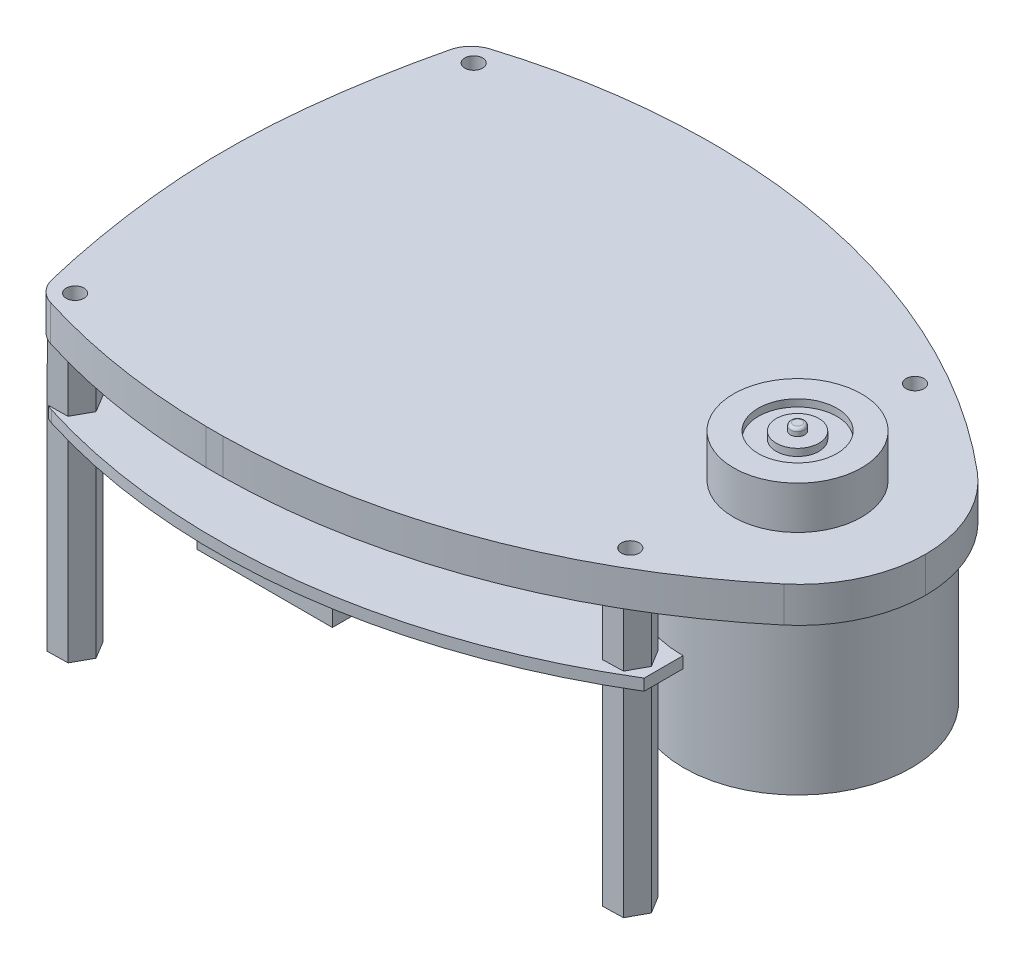
SolidWorks part; units mm, degrees
ref_plane "Спереди" through (0, 0, 0) normal (0, 0, 1) x (1, 0, 0)
ref_plane "Сверху" through (0, 0, 0) normal (0, 1, 0) x (1, 0, 0)
ref_plane "Справа" through (0, 0, 0) normal (1, 0, 0) x (0, 0, -1)
sketch "Эскиз1" plane through (0, 0, 0) normal (0, 1, 0) x (1, 0, 0)
  line L1 (-49.25, 35) -> (49.25, 35)
  line L2 (-49.25, 35) -> (-49.25, -35)
  line L3 (-49.25, -35) -> (49.25, -35)
  line L4 (49.25, 35) -> (49.25, -35)
  line L5 (-49.25, 35) -> (49.25, -35) construction
  line L6 (-49.25, -35) -> (49.25, 35) construction
  point P0 (0, 0)
  dimension "D1" = 98.5
  dimension "D2" = 70
extrude "Бобышка-Вытянуть1" add sketch "Эскиз1" along normal blind 5
sketch "Эскиз2" plane through (0, 5, 0) normal (0, 1, 0) x (1, 0, 0)
  line L0 (-49.25, 35) -> (-49.25, -35) construction
  circle A0 centre (-14.25, 0) radius 35
  point P2 (-49.25, 0)
  point P3 (-49.25, 0)
extrude "Бобышка-Вытянуть2" add sketch "Эскиз2" along normal blind 28.1
sketch "Эскиз3" plane through (0, 33.1, 0) normal (0, 1, 0) x (1, 0, 0)
  line L0 (-14.25, 0) -> (-14.25, 50000) construction
  line L1 (-14.25, -20) -> (-26.2883, -20) construction
  line L2 (-49.25, -35) -> (-14.25, -35) construction
  circle A0 centre (-14.25, 28.5) radius 2
  circle A1 centre (-34.5539, -20) radius 2
  circle A2 centre (6.0539, -20) radius 2
  arc A3 (-49.25, 0) -> (-14.25, -35) centre (-14.25, 0) ccw construction
  circle A4 centre (-14.25, 0) radius 35 construction
  dimension "D2" = 4
  dimension "D1" = 6.5
  dimension "D3" = 15
  dimension "D4" = 28.5
  dimension "D5" = 28.5
extrude "Вырез-Вытянуть1" cut sketch "Эскиз3" against normal blind 5
fillet "Скругление1" radius 2 1 edges at (-14.25, 33.1, 35)
fillet "Скругление2" radius 1 3 edges at (6.0539, 33.1, 22) (-34.5539, 33.1, 22) (-14.25, 33.1, -26.5)
sketch "Эскиз4" plane through (0, 33.1, 0) normal (0, 1, 0) x (1, 0, 0)
  line L0 (-22.1152, -6.9149) -> (-22.1152, -0.8316)
  line L1 (-22.1152, -0.8316) -> (-19.0735, -0.8316)
  line L2 (-19.0735, -0.8316) -> (-19.0735, -5.8538)
  line L3 (-19.0735, -5.8538) -> (-21.2663, -5.8538)
  line L4 (-21.2663, -5.8538) -> (-21.2663, -6.9149)
  line L5 (-21.2663, -6.9149) -> (-22.1152, -6.9149)
  line L6 (-22.1152, 0) -> (-22.1152, 5.1201)
  line L7 (-22.1152, 5.1201) -> (-19.0735, 5.1201)
  line L8 (-19.0735, 5.1201) -> (-19.0735, 4.2707)
  line L9 (-19.0735, 4.2707) -> (-21.2663, 4.2707)
  line L10 (-21.2663, 4.2707) -> (-21.2663, 0)
  line L11 (-21.2663, 0) -> (-22.1152, 0)
  line L12 (-21.2663, -1.9579) -> (-20.1699, -1.9579)
  line L13 (-20.1699, -1.9579) -> (-20.1699, -4.9509)
  line L14 (-20.1699, -4.9509) -> (-21.2663, -4.9509)
  line L15 (-21.2663, -4.9509) -> (-21.2663, -1.9579)
  line L16 (-13.8296, 0) -> (-13.8296, 6.293)
  line L17 (-18.1168, 0) -> (-14.8003, 0)
  line L18 (-18.1168, 0) -> (-18.1168, 5.1201)
  line L19 (-18.1168, 5.1201) -> (-14.8003, 5.1201)
  line L20 (-14.8003, 0) -> (-14.8003, 5.1201)
  line L21 (-9.8255, 5.1201) -> (-6.5494, 5.1201)
  line L22 (-9.8255, 5.1201) -> (-9.8255, 0)
  line L23 (-9.8255, 0) -> (-6.5494, 0)
  line L24 (-6.5494, 5.1201) -> (-6.5494, 0)
  line L25 (-8.9357, 4.2707) -> (-7.3988, 4.2707)
  line L26 (-8.9357, 4.2707) -> (-8.9357, 0.9137)
  line L27 (-8.9357, 0.9137) -> (-7.3988, 0.9137)
  line L28 (-7.3988, 4.2707) -> (-7.3988, 0.9137)
  line L29 (-17.3079, 4.2707) -> (-15.6497, 4.2707)
  line L30 (-17.3079, 4.2707) -> (-17.3079, 0.9137)
  line L31 (-17.3079, 0.9137) -> (-15.6497, 0.9137)
  line L32 (-15.6497, 4.2707) -> (-15.6497, 0.9137)
  line L33 (-12.9802, 4.2707) -> (-11.6455, 4.2707)
  line L34 (-12.9802, 4.2707) -> (-12.9802, 0.9137)
  line L35 (-12.9802, 0.9137) -> (-11.6455, 0.9137)
  line L36 (-11.6455, 4.2707) -> (-11.6455, 0.9137)
  line L37 (-12.9802, -4.142) -> (-11.6455, -4.142)
  line L38 (-12.9802, -4.142) -> (-12.9802, -5.1936)
  line L39 (-12.9802, -5.1936) -> (-11.6455, -5.1936)
  line L40 (-11.6455, -4.142) -> (-11.6455, -5.1936)
  line L41 (-16.9439, -1.9579) -> (-15.6497, -1.9579)
  line L42 (-16.9439, -1.9579) -> (-16.9439, -3.0499)
  line L43 (-16.9439, -3.0499) -> (-15.6497, -3.0499)
  line L44 (-15.6497, -1.9579) -> (-15.6497, -3.0499)
  line L46 (-7.5508, -0.7643) -> (-6.5494, -0.7643)
  line L47 (-7.5508, -0.7643) -> (-7.5508, -2.8858)
  line L48 (-7.5508, -2.8858) -> (-6.5494, -2.8858)
  line L49 (-6.5494, -0.7643) -> (-6.5494, -2.8858)
  line L50 (-6.5494, -6.9149) -> (-7.5508, -6.9149)
  line L51 (-6.5494, -6.9149) -> (-6.5494, -4.0216)
  line L52 (-6.5494, -4.0216) -> (-7.5508, -4.0216)
  line L53 (-13.8296, 6.293) -> (-12.9802, 6.293)
  line L54 (-12.9802, 6.293) -> (-12.9802, 5.1201)
  line L55 (-12.9802, 5.1201) -> (-10.7153, 5.1201)
  line L56 (-10.7153, 5.1201) -> (-10.7153, 0)
  line L57 (-10.7153, 0) -> (-13.8296, 0)
  line L58 (-9.8255, -0.8316) -> (-8.6437, -0.8316)
  line L59 (-8.6437, -0.8316) -> (-8.6437, -2.9608)
  line L60 (-8.6437, -2.9608) -> (-7.5508, -2.9608)
  line L61 (-9.8255, -0.8316) -> (-9.8255, -5.8538)
  line L62 (-9.8255, -5.8538) -> (-8.6437, -5.8538)
  line L63 (-8.6437, -5.8538) -> (-8.6437, -3.9573)
  line L64 (-8.6437, -3.9573) -> (-7.5508, -3.9573)
  line L65 (-7.5508, -2.9608) -> (-7.5508, -3.9573)
  line L66 (-13.8296, -0.8316) -> (-10.7153, -0.8316)
  line L67 (-10.7153, -0.8316) -> (-10.7153, -5.8538)
  line L68 (-10.7153, -5.8538) -> (-13.8296, -5.8538)
  line L69 (-13.8296, -5.8538) -> (-13.8296, -3.0499)
  line L70 (-13.8296, -3.0499) -> (-11.6455, -3.0499)
  line L71 (-11.6455, -3.0499) -> (-11.6455, -1.9408)
  line L72 (-11.6455, -1.9408) -> (-13.8296, -1.9408)
  line L73 (-13.8296, -1.9408) -> (-13.8296, -0.8316)
  line L74 (-18.1168, -0.8316) -> (-14.8003, -0.8316)
  line L75 (-14.8003, -0.8316) -> (-14.8003, -4.142)
  line L76 (-14.8003, -4.142) -> (-16.9439, -4.142)
  line L77 (-16.9439, -4.142) -> (-16.9439, -4.9509)
  line L78 (-16.9439, -4.9509) -> (-14.8003, -4.9509)
  line L79 (-14.8003, -4.9509) -> (-14.8003, -5.8538)
  line L80 (-14.8003, -5.8538) -> (-18.1168, -5.8538)
  line L81 (-18.1168, -5.8538) -> (-18.1168, -0.8316)
  line L82 (-7.5508, -6.9149) -> (-7.5508, -4.0216)
  circle A0 centre (-14.25, 0) radius 13
  dimension "D1" = 26
extrude "Вырез-Вытянуть3" cut sketch "Эскиз4" against normal blind 0.5 contours A0 L50 L82 L52 L51 L72 L73 L66 L67 L68 L69 L70 L71 L56 L57 L16 L53 L54 L55 L10 L11 L6 L7 L8 L9 L4 L5 L0 L1 L2 L3 L20 L17 L18 L19 L21 L24 L23 L22 L46 L49 L48 L47 | L32 L29 L30 L31 | L36 L33 L34 L35 | L28 L25 L26 L27 | L44 L41 L42 L43 | L15 L14 L13 L12 | L37 L40 L39 L38 region at (-20.7181, 33.1, 3.4544) region at (-8.1672, 33.1, -2.5922) region at (-16.4788, 33.1, -2.5922) region at (-12.3129, 33.1, -2.5922) region at (-16.2968, 33.1, 2.5039) region at (-14.2871, 33.1, -0.0991)
sketch "Эскиз5" plane through (0, 5, 0) normal (0, 1, 0) x (1, 0, 0)
  line L0 (-42.25, 30.7255) -> (-42.25, -39.5827) construction
  line L1 (27.75, 26.9972) -> (27.75, -49973.0028) construction
  line L2 (-49.25, 0) -> (49950.75, 0) construction
  circle A0 centre (-14.25, 0) radius 33 construction
  circle A1 centre (-42.25, 28) radius 1.25
  circle A2 centre (27.75, 20) radius 1.25
  circle A3 centre (27.75, -20) radius 1.25
  circle A4 centre (-42.25, -28) radius 1.25
  point P4 (-14.25, 33)
  dimension "D1" = 28
  dimension "D3" = 2.5
  dimension "D2" = 42
  dimension "D4" = 28
  dimension "D5" = 20
extrude "Вырез-Вытянуть4" cut sketch "Эскиз5" against normal blind 5
sketch "Эскиз6" plane through (0, 5, 0) normal (0, 1, 0) x (1, 0, 0)
  line L0 (49.25, 0) -> (50049.25, 0) construction
  line L1 (49.25, -35) -> (49.25, 35) construction
  circle A0 centre (31.25, 0) radius 9
  arc A1 (-14.25, -35) -> (-14.25, 35) centre (-14.25, 0) ccw construction
  point P4 (49.25, 0)
  dimension "D1" = 18
  dimension "D2" = 45.5
extrude "Бобышка-Вытянуть3" add sketch "Эскиз6" along normal blind 7
sketch "Эскиз7" plane through (0, 12, 0) normal (0, 1, 0) x (1, 0, 0)
  circle A0 centre (31.25, 0) radius 9
  circle A1 centre (31.25, 0) radius 0.9935
extrude "Вырез-Вытянуть5" cut sketch "Эскиз7" against normal blind 1
sketch "Эскиз8" plane through (0, 11, 0) normal (0, 1, 0) x (1, 0, 0)
  circle A0 centre (31.25, 0) radius 3.0011
  circle A1 centre (31.25, 0) radius 5.5217
extrude "Вырез-Вытянуть6" cut sketch "Эскиз8" against normal blind 1
fillet "Скругление3" radius 0.4 1 edges at (31.25, 12, 0.9935)
sketch "Эскиз9" plane through (0, 5, 0) normal (0, 1, 0) x (1, 0, 0)
  circle A0 centre (31.25, 0) radius 16
  dimension "D1" = 32
extrude "Бобышка-Вытянуть4" add sketch "Эскиз9" against normal blind 27
sketch "Эскиз10" plane through (0, 0, 0) normal (0, -1, 0) x (1, 0, 0)
  line L0 (-49.25, 0) -> (49950.75, 0) construction
  line L1 (-40.8546, 25.4729) -> (-39.3638, 27.9449)
  line L2 (-39.3638, 27.9449) -> (-40.7592, 30.472)
  line L3 (-40.7592, 30.472) -> (-43.6454, 30.5271)
  line L4 (-43.6454, 30.5271) -> (-45.1362, 28.0551)
  line L5 (-45.1362, 28.0551) -> (-43.7408, 25.528)
  line L6 (-43.7408, 25.528) -> (-40.8546, 25.4729)
  line L7 (29.2571, 22.4621) -> (26.3713, 22.5363)
  line L8 (26.3713, 22.5363) -> (24.8642, 20.0742)
  line L9 (24.8642, 20.0742) -> (26.2429, 17.5379)
  line L10 (26.2429, 17.5379) -> (29.1287, 17.4637)
  line L11 (29.1287, 17.4637) -> (30.6358, 19.9258)
  line L12 (30.6358, 19.9258) -> (29.2571, 22.4621)
  line L13 (30.6358, -19.9258) -> (29.2571, -22.4621)
  line L14 (29.1287, -17.4637) -> (30.6358, -19.9258)
  line L15 (26.2429, -17.5379) -> (29.1287, -17.4637)
  line L16 (24.8642, -20.0742) -> (26.2429, -17.5379)
  line L17 (26.3713, -22.5363) -> (24.8642, -20.0742)
  line L18 (29.2571, -22.4621) -> (26.3713, -22.5363)
  line L19 (-43.7408, -25.528) -> (-40.8546, -25.4729)
  line L20 (-45.1362, -28.0551) -> (-43.7408, -25.528)
  line L21 (-43.6454, -30.5271) -> (-45.1362, -28.0551)
  line L22 (-40.7592, -30.472) -> (-43.6454, -30.5271)
  line L23 (-39.3638, -27.9449) -> (-40.7592, -30.472)
  line L24 (-40.8546, -25.4729) -> (-39.3638, -27.9449)
  circle A0 centre (-42.25, 28) radius 2.5 construction
  circle A1 centre (27.75, 20) radius 2.5 construction
  circle A2 centre (27.75, -20) radius 2.5 construction
  circle A3 centre (-42.25, -28) radius 2.5 construction
  point P17 (27.75, 20)
  dimension "D1" = 5
  dimension "D2" = 5
extrude "Бобышка-Вытянуть5" add sketch "Эскиз10" along normal blind 38
sketch "Эскиз11" plane through (0, 5, 0) normal (0, 1, 0) x (1, 0, 0)
  circle A0 centre (-14.25, 0) radius 26
  dimension "D1" = 52
extrude "Бобышка-Вытянуть6" add sketch "Эскиз11" against normal blind 8
fillet "Скругление4" radius 1 1 edges at (-14.25, -3, 26)
sketch "Эскиз12" plane through (0, 5, 0) normal (0, 1, 0) x (1, 0, 0)
  line L1 (49.25, -35) -> (49.25, 35) construction
  line L2 (-49.25, 0) -> (-50049.25, 0) construction
  line L4 (-54.0511, 37.7308) -> (52.2004, 37.7308)
  line L5 (-54.0511, 37.7308) -> (-54.0511, -37.8351)
  line L6 (-54.0511, -37.8351) -> (52.2004, -37.8351)
  line L7 (52.2004, 37.7308) -> (52.2004, -37.8351)
  arc A0 (-49.25, 0) -> (-45.5286, 27.9743) centre (86.6751, -3.8473) cw
  circle A1 centre (-14.25, 0) radius 35 construction
  arc A3 (49.25, 0) -> (42.909, 13.5993) centre (31.4018, -0.0442) ccw
  arc A4 (-49.25, 0) -> (-14.25, -35) centre (-14.25, 0) ccw construction
  arc A5 (-42.835, 30.8555) -> (42.909, 13.5993) centre (-15.6796, -55.8665) cw
  arc A6 (-45.5286, 27.9743) -> (-42.835, 30.8555) centre (-41.6397, 27.0383) cw
  arc A7 (-45.5286, -27.9743) -> (-42.835, -30.8555) centre (-41.6397, -27.0383) ccw
  arc A8 (-42.835, -30.8555) -> (42.909, -13.5993) centre (-15.6796, 55.8665) ccw
  arc A9 (49.25, 0) -> (42.909, -13.5993) centre (31.4018, 0.0442) cw
  arc A10 (-49.25, 0) -> (-45.5286, -27.9743) centre (86.6751, 3.8473) ccw
  dimension "D1" = 4
extrude "Вырез-Вытянуть7" cut sketch "Эскиз12" against normal blind 8
fillet "Скругление5" radius 100 1 edges at (-49.25, 2.5, 0)
sketch "Эскиз13" plane through (0, 0, 0) normal (0, -1, 0) x (1, 0, 0)
  line L0 (31.5536, 21.8603) -> (31.5536, 16.4)
  line L1 (31.5536, -16.4) -> (31.5536, -21.8603)
  arc A0 (-49.0982, 0) -> (-45.3768, 27.9743) centre (86.8269, -3.8473) cw
  arc A1 (31.5536, 16.4) -> (31.5536, -16.4) centre (31.5536, 0) ccw
  arc A2 (-42.6831, 30.8555) -> (31.5536, 21.8603) centre (-15.5278, -55.8665) cw
  arc A3 (-45.3768, 27.9743) -> (-42.6831, 30.8555) centre (-41.4878, 27.0383) cw
  arc A4 (-45.3768, -27.9743) -> (-42.6831, -30.8555) centre (-41.4878, -27.0383) ccw
  arc A5 (-42.6831, -30.8555) -> (31.5536, -21.8603) centre (-15.5278, 55.8665) ccw
  arc A7 (-49.0982, 0) -> (-45.3768, -27.9743) centre (86.8269, 3.8473) ccw
  arc A8 (-48.5248, 10.6929) -> (-48.5248, -10.6929) centre (50.9018, 0) ccw construction
  point P16 (-49.0982, 0)
  point P21 (-49.0982, 0)
  dimension "D1" = 4
  dimension "D2" = 32.8
extrude "Бобышка-Вытянуть7" add sketch "Эскиз13" along normal blind 1.6 from offset 8
sketch "Эскиз14" plane through (0, -9.6, 0) normal (0, -1, 0) x (1, 0, 0)
  line L1 (-24.0982, 30) -> (-4.0982, 30)
  line L2 (-24.0982, 30) -> (-24.0982, 25)
  line L3 (-24.0982, 25) -> (-4.0982, 25)
  line L4 (-4.0982, 30) -> (-4.0982, 25)
  circle A0 centre (-14.25, 0) radius 35 construction
  point P4 (-14.0982, 30)
  dimension "D1" = 5
  dimension "D2" = 20
  dimension "D3" = 35
  dimension "D4" = 30
extrude "Бобышка-Вытянуть8" add sketch "Эскиз14" along normal blind 6
chamfer "Фаска1" distance 1 angle 45 1 edges at (-24.0982, -12.6, 30)
sketch "Sketch1" plane through (0, 33.1, 0) normal (0, 1, 0) x (1, 0, 0)
  circle A0 centre (-14.25, 0) radius 35 construction
  circle A1 centre (-14.25, 0) radius 35
extrude "Cut-Extrude1" cut sketch "Sketch1" against normal up to vertex (28.1 mm away) up to point (42.909, 5, -13.5993)
